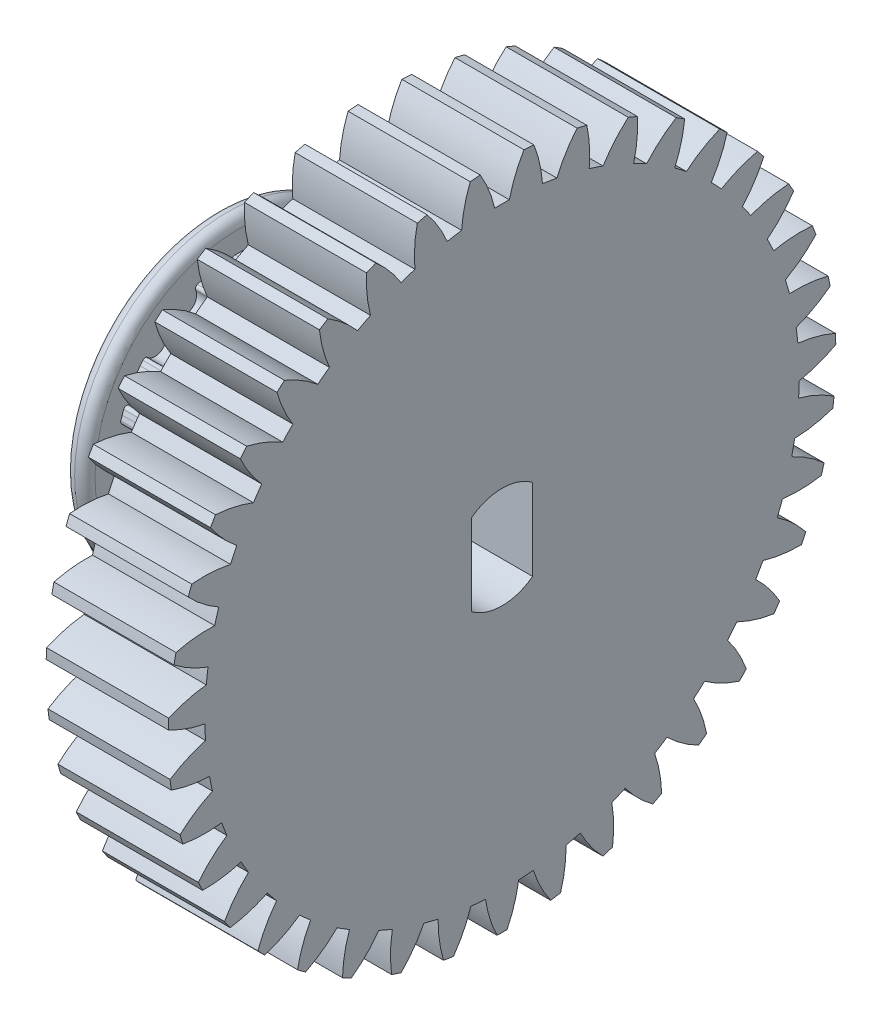
SolidWorks part; units mm, degrees
ref_plane "Plane1" through (0, 0, 0) normal (0, 0, 1) x (1, 0, 0)
ref_plane "Plane2" through (0, 0, 0) normal (0, 1, 0) x (1, 0, 0)
ref_plane "Plane3" through (0, 0, 0) normal (1, 0, 0) x (0, 0, -1)
sketch "HoldingSke" plane through (0, 0, 0) normal (0, 1, 0) x (1, 0, 0)
  line L0 (0, 0) -> (0.9714, -0.7867)
  line L1 (-15, 0) -> (100, 0) construction
  line L2 (0, 0) -> (-2.1039, 2.3779)
  line L3 (0, 0) -> (-11.863, 4.5341)
  line L4 (0, 0) -> (6.7114, 5.4348)
  line L5 (0, 0) -> (-46.8476, -17.4728)
  line L6 (0, 0) -> (-9.9476, -6.7116)
  line L7 (-2.1039, 2.3779) -> (8.6589, 51.2072)
  line L8 (-76.2, 54.61) -> (-75.3, 54.61)
  line L9 (-71.009, 38.7566) -> (-53.1078, 45.2721)
  line L10 (-76.2, 71.12) -> (104.1128, 71.12)
  line L11 (0, 0) -> (-12, 0)
  line L12 (-76.2, 101.6) -> (-76.17, 101.6)
  line L13 (24.9733, 27.94) -> (52.9518, 28.4284)
  line L14 (24.9733, 27.94) -> (24.9743, 27.94)
  line L15 (24.9733, 27.94) -> (100.4006, 29.5858)
  line L16 (-63.627, -0.8) -> (-12.827, -0.8)
  circle A0 centre (0, 0) radius 2.5
  circle A1 centre (0, 0) radius 14.599
  circle A2 centre (0, 0) radius 37.5
  circle A3 centre (0, 0) radius 2.5
  dimension "Num_teeth" = 39
  dimension "Pitch_radius" = 180.3128
  dimension "Width" = 12
sketch "BasProSke" plane through (0, 0, 0) normal (0, 1, 0) x (1, 0, 0)
  line L0 (-10, 0) -> (60, 0) construction
  line L1 (0, 0) -> (0, 16.4)
  line L2 (0, 0) -> (6, 0)
  line L3 (6, 0) -> (6, 16.4)
  line L4 (6, 16.4) -> (0, 16.4)
  dimension "Thickness" = 6
  dimension "Diameter" = 32.8
revolve "Base-Revolve" add sketch "BasProSke" angle 360 about L0
sketch "TooCutSke" plane through (0, 0, 0) normal (1, 0, 0) x (0, 0, -1)
  line L1 (0, 0) -> (0, 107) construction
  line L2 (0, 0) -> (-0.6806, 15.5851) construction
  line L3 (0, 0) -> (-2.5088, 31.0776) construction
  line L4 (-0.6806, 15.5851) -> (-1.2544, 15.5388) construction
  arc A0 (0.3593, 14.5946) -> (-0.3593, 14.5946) centre (0, 0) ccw
  arc A1 (1.0886, 16.3893) -> (-1.0886, 16.3893) centre (0, 0) ccw
  circle A2 centre (0, 0) radius 15.6 construction
  circle A3 centre (0, 0) radius 14.6592 construction
  arc A4 (-0.3593, 14.5946) -> (-1.0886, 16.3893) centre (-6.4349, 13.1714) ccw
  arc A5 (1.0886, 16.3893) -> (0.3593, 14.5946) centre (6.4349, 13.1714) ccw
extrude "ToothCut" cut sketch "TooCutSke" along normal through all
fillet "Breaks" [suppressed] radius 0.016 tangent propagation no
fillet "RootFillets" [suppressed] radius 0.201
pattern_circular "TeethCuts" count 39 every 9.231 about axis through (-10, 0, 0) along (1, 0, 0) of "ToothCut", "RootFillets", "Breaks"
sketch "HubNeaOneSke" plane through (0, 0, 0) normal (-1, 0, 0) x (0, 0, 1)
  circle A0 centre (0, 0) radius 14.599
  dimension "Diameter" = 29.198
extrude "HubNearOne" [suppressed] add sketch "HubNeaOneSke" along normal blind 44.0014
sketch "HubNeaBotSke" plane through (0, 0, 0) normal (-1, 0, 0) x (0, 0, 1)
  circle A0 centre (0, 0) radius 14.599
  dimension "Diameter" = 29.198
extrude "HubNearBoth" [suppressed] add sketch "HubNeaBotSke" along normal blind 22.0007
ref_plane "FarPln" through (6, 0, 0) normal (1, 0, 0) x (0, 0, -1)
sketch "HubFarSke" plane through (6, 0, 0) normal (1, 0, 0) x (0, 0, -1)
  circle A0 centre (0, 0) radius 14.599
  dimension "Diameter" = 29.198
extrude "HubFar" [suppressed] add sketch "HubFarSke" along normal blind 22.0007
sketch "BorSke" plane through (0, 0, 0) normal (1, 0, 0) x (0, 0, -1)
  circle A0 centre (0, 0) radius 2.5
  dimension "Diameter" = 5
extrude "Bore" cut sketch "BorSke" along normal mid plane 100.0027
sketch "KeySke" plane through (0, 0, 0) normal (1, 0, 0) x (0, 0, -1)
  line L0 (-1, 0) -> (-1, 3.4)
  line L1 (-1, 3.4) -> (1, 3.4)
  line L2 (1, 3.4) -> (1, 0)
  line L3 (0, 0) -> (0, 34) construction
  line L4 (-1, 0) -> (1, 0)
  dimension "Width" = 2
extrude "Keyway" [suppressed] cut sketch "KeySke" along normal mid plane 100.0027
pattern_circular "Keyway2" [suppressed] count 2 every 90 about axis through (-10, 0, 0) along (1, 0, 0) reverse direction yes
sketch "Sketch1" plane through (0, 0, 0) normal (-1, 0, 0) x (0, 0, 1)
  circle A0 centre (0, 0) radius 6.366
  dimension "D1" = 12.732
extrude "Boss-Extrude1" add sketch "Sketch1" along normal blind 7
sketch "Sketch2" plane through (-7, 0, 0) normal (-1, 0, 0) x (0, 0, 1)
  line L0 (0, 0) -> (-0.106, 6.3651) construction
  line L1 (-0.0997, 5.9852) -> (0.1182, 5.9852)
  line L2 (0, 0) -> (0.814, 5.7588) construction
  line L3 (-0.0997, 5.9852) -> (-0.106, 6.3651)
  line L5 (1.7547, 5.723) -> (1.5453, 5.7834)
  line L6 (1.7547, 5.723) -> (1.8661, 6.0863)
  line L9 (-0.106, 6.3651) -> (0.814, 6.4142)
  line L10 (0.814, 6.4142) -> (0.9696, 6.3651)
  line L11 (1.8661, 6.0863) -> (0.9696, 6.3651)
  circle A0 centre (0, 0) radius 6.366 construction
  arc A1 (0.1182, 5.9852) -> (0.2673, 5.8188) centre (0.1182, 5.8352) cw
  arc A2 (0.2673, 5.8188) -> (1.356, 5.6649) centre (0.814, 5.7588) ccw
  circle A8 centre (0, 0) radius 6.366 construction
  arc A9 (1.5453, 5.7834) -> (1.356, 5.6649) centre (1.5038, 5.6393) ccw
  dimension "D1" = 0.15
  dimension "D2" = 0.55
  dimension "D3" = 0.38
  dimension "D5" = 9
extrude "Cut-Extrude6" cut sketch "Sketch2" against normal blind 7
pattern_circular "CirPattern1" count 20 over 360 about axis through (-7, 0, 0) along (-1, 0, 0) of "Cut-Extrude6"
sketch "Sketch3" plane through (0, 0, 0) normal (1, 0, 0) x (0, 0, -1)
  circle A1 centre (0, 0) radius 2.5
  circle A2 centre (0, 0) radius 2.5
  dimension "D1" = 0
extrude "Cut-Extrude7" cut sketch "Sketch3" against normal blind 7
sketch "Sketch4" plane through (-7, 0, 0) normal (-1, 0, 0) x (0, 0, 1)
  circle A0 centre (0, 0) radius 7.4986
extrude "Boss-Extrude2" add sketch "Sketch4" along normal blind 1
fillet "Fillet1" radius 0.5 2 edges at (-7, 0, 7.4986) (-8, 0, 7.4986)
sketch "Sketch5" plane through (-7, 0, 0) normal (1, 0, 0) x (0, 0, -1)
  circle A1 centre (0, 0) radius 2.5
  circle A2 centre (0, 0) radius 2.5
  dimension "D1" = 0
extrude "Cut-Extrude8" cut sketch "Sketch5" against normal blind 1
sketch "Sketch6" plane through (-8, 0, 0) normal (-1, 0, 0) x (0, 0, 1)
  line L0 (-1.5, 0) -> (1.5, 0) construction
  line L1 (-1.5, -2) -> (-1.5, 2)
  line L2 (1.5, -2) -> (1.5, 2)
  circle A0 centre (0, 0) radius 2.5 construction
  arc A1 (-1.5, 2) -> (-1.5, -2) centre (0, 0) ccw
  arc A2 (1.5, 2) -> (1.5, -2) centre (0, 0) cw
  point P4 (0, 0)
  point P10 (-1.5, 0)
  point P13 (1.5, 0)
  circle M2 centre (0, 0) radius 2.5
extrude "Boss-Extrude3" add sketch "Sketch6" against normal blind 14 contours L1 M2 | L2 M2 region at (-8, 0, -1.9078) region at (-8, 0, 1.9078)
equation "' \"Module@HoldingSke\" = 6.35"
equation "' \"Num_teeth@HoldingSke\" = 12"
equation "' \"Ap@HoldingSke\" =  20"
equation "' \"Ap@HoldingSke\" = 20"
equation "' \"Width@HoldingSke\" = 0.5 * 25.4"
equation "' \"Hub_dia@HoldingSke\"= 1 * 25.4"
equation "' \"Hub_dia@HoldingSke\" = 1 * 25.4"
equation "' \"Overall_len@HoldingSke\" = 1.0 * 25.4"
equation "' \"Bore@HoldingSke\" = 0.75 * 25.4"
equation "' \"T_dim@HoldingSke\" = 0.1 * 25.4"
equation "' \"Width@KeySke\" = 0.25 * 25.4"
equation "' \"Show_teeth@HoldingSke\" = 13"
equation "' \"Backlash@HoldingSke\" = 0.009 * 25.4"
equation "' \"Addendum_fac@HoldingSke\" = 1.0"
equation "' \"Dedendum_fac@HoldingSke\" = 1.25"
equation "' \"Dedendum_add@HoldingSke\" = 0.00005 * 25.4"
equation "' \"Clearance_fac@HoldingSke\" = 0.25"
equation "\"Pitch@HoldingSke\" = 1 / \"Module@HoldingSke\""
equation "\"Overcut_dia@TooCutSke\" = (\"Num_teeth@HoldingSke\" + 2 * \"Addendum_fac@HoldingSke\") / \"Pitch@HoldingSke\" + 0.002 * 25.4"
equation "\"Pitch_dia@TooCutSke\" = \"Num_teeth@HoldingSke\" / \"Pitch@HoldingSke\""
equation "\"Base_dia@TooCutSke\" = \"Num_teeth@HoldingSke\" / \"Pitch@HoldingSke\" * cos((\"Ap@HoldingSke\"  * 3.14159265 / 180))"
equation "\"Root_dia@TooCutSke\" = (\"Num_teeth@HoldingSke\" + 2) / \"Pitch@HoldingSke\" - 2 * (\"Addendum_fac@HoldingSke\" + \"Dedendum_fac@HoldingSke\") / \"Pitch@HoldingSke\" - \"Dedendum_add@HoldingSke\" * 2"
equation "\"Half_ang@TooCutSke\" = 180 / \"Num_teeth@HoldingSke\""
equation "\"Half_CT@TooCutSke\" = \"Num_teeth@HoldingSke\" / \"Pitch@HoldingSke\" * sin((3.14159265 / 2 / \"Num_teeth@HoldingSke\")) / 2 - 7 * \"Backlash@HoldingSke\" / 4"
equation "\"Flank_rad@TooCutSke\" = \"Num_teeth@HoldingSke\" / \"Pitch@HoldingSke\" / 5"
equation "\"Radius@RootFillets\" = \"Clearance_fac@HoldingSke\" / \"Pitch@HoldingSke\" + \"Dedendum_add@HoldingSke\""
equation "\"Break_rad@Breaks\" = 0.02 / \"Pitch@HoldingSke\""
equation "\"Thickness@HoldingSke\" = \"Width@HoldingSke\""
equation "\"OAL@HoldingSke\" = \"Thickness@HoldingSke\""
equation "\"MHD@HoldingSke\" = (\"Num_teeth@HoldingSke\" + 2) / \"Pitch@HoldingSke\" - 2 * (\"Addendum_fac@HoldingSke\" + \"Dedendum_fac@HoldingSke\")  / \"Pitch@HoldingSke\" - \"Dedendum_add@HoldingSke\" * 2"
equation "\"MBD@HoldingSke\" = (\"Num_teeth@HoldingSke\" + 2) / \"Pitch@HoldingSke\" - 2 * (\"Addendum_fac@HoldingSke\" + \"Dedendum_fac@HoldingSke\")  / \"Pitch@HoldingSke\" - \"Dedendum_add@HoldingSke\" * 2 - 0.002 * 25.4"
equation "\"MHD@HoldingSke\" = ((sgn( \"MHD@HoldingSke\" - \"Hub_dia@HoldingSke\" )-1)*( \"MHD@HoldingSke\" - \"Hub_dia@HoldingSke\" ))/-2+ \"Hub_dia@HoldingSke\""
equation "\"MBD@HoldingSke\" = ((sgn( \"MBD@HoldingSke\" - \"Bore@HoldingSke\" )-1)*( \"MBD@HoldingSke\" - \"Bore@HoldingSke\" ))/-2+ \"Bore@HoldingSke\""
equation "\"OAL@HoldingSke\" = ((sgn( \"OAL@HoldingSke\" - \"Overall_len@HoldingSke\" )+1)*( \"OAL@HoldingSke\" - \"Overall_len@HoldingSke\" ))/2 + \"Overall_len@HoldingSke\" + 0.000002 * 25.4"
equation "\"Num_teeth@TeethCuts\" = int( \"Show_teeth@HoldingSke\" ) + 1"
equation "\"Num_teeth@TeethCuts\" = ((sgn( \"Num_teeth@TeethCuts\" - \"Num_teeth@HoldingSke\" )-1)*( \"Num_teeth@TeethCuts\" - \"Num_teeth@HoldingSke\" ))/-2+ \"Num_teeth@HoldingSke\""
equation "\"Num_teeth@TeethCuts\" = ((sgn( \"Num_teeth@TeethCuts\" - 2.0)+1)*( \"Num_teeth@TeethCuts\" - 2.0))/2 +2.0"
equation "\"Angle@TeethCuts\" = 360.0 / \"Num_teeth@HoldingSke\""
equation "\"Diameter@BasProSke\" = (\"Num_teeth@HoldingSke\" + 2 * \"Addendum_fac@HoldingSke\") / \"Pitch@HoldingSke\""
equation "'\"Fillet_rad@BasProSke\" =  \"Thickness@HoldingSke\" * 0.05"
equation "'\"Fillet_rad@BasProSke\" = \"Thickness@HoldingSke\" * 0.05"
equation "\"MHD@HoldingSke\" = ((sgn( \"MHD@HoldingSke\" - \"Root_dia@TooCutSke\" )-1)*( \"MHD@HoldingSke\" - \"Root_dia@TooCutSke\" ))/-2+ \"Root_dia@TooCutSke\""
equation "\"Diameter@HubNeaOneSke\" = \"MHD@HoldingSke\""
equation "\"Length@HubNearOne\" = \"OAL@HoldingSke\" - \"Thickness@BasProSke\""
equation "\"Diameter@HubNeaBotSke\" = \"MHD@HoldingSke\""
equation "\"Length@HubNearBoth\" = ( \"OAL@HoldingSke\" - \"Thickness@BasProSke\" ) / 2.0"
equation "\"Thickness@FarPln\" = \"Thickness@BasProSke\""
equation "\"Diameter@HubFarSke\" = \"MHD@HoldingSke\""
equation "\"Length@HubFar\" = ( \"OAL@HoldingSke\" - \"Thickness@BasProSke\" ) / 2.0"
equation "\"Diameter@BorSke\" = \"MBD@HoldingSke\""
equation "\"D1@Bore\" = \"OAL@HoldingSke\" * 2.0"
equation "\"D1@Keyway\" = \"OAL@HoldingSke\" * 2.0"
equation "\"Offset@KeySke\" = \"T_dim@HoldingSke\" + \"MBD@HoldingSke\" / 2.0"
equation "\"n\"= 20"
equation "\"p\"= 2"
equation "\"pd\"= \"n\" * \"p\" / pi"
equation "\"D5@Sketch2\"=180/\"n\""
